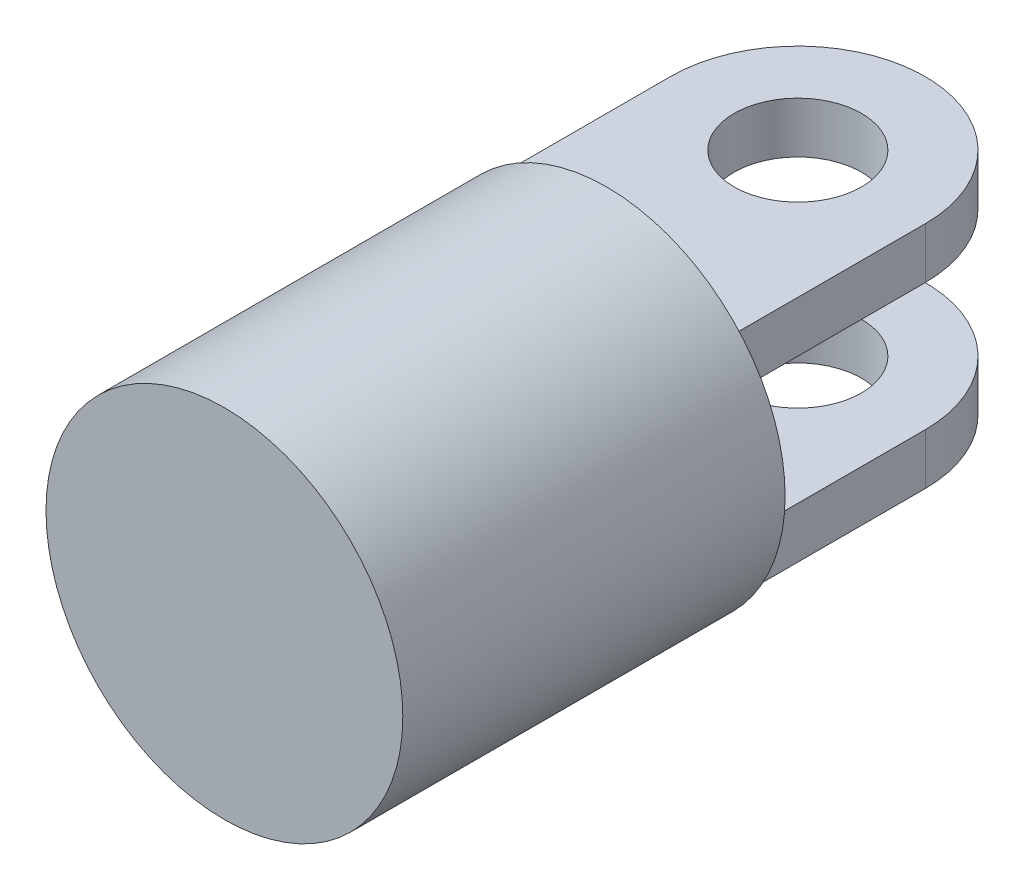
SolidWorks part; units mm, degrees
ref_plane "前视基准面" through (0, 0, 0) normal (0, 0, 1) x (1, 0, 0)
ref_plane "上视基准面" through (0, 0, 0) normal (0, 1, 0) x (1, 0, 0)
ref_plane "右视基准面" through (0, 0, 0) normal (1, 0, 0) x (0, 0, -1)
sketch "草图1" plane through (0, 0, 0) normal (0, 0, 1) x (1, 0, 0)
  circle A0 centre (0, 0) radius 14
  dimension "D1" = 28
extrude "凸台-拉伸1" add sketch "草图1" along normal blind 30
sketch "草图2" plane through (0, 0, 0) normal (0, 1, 0) x (1, 0, 0)
  line L0 (10, 15) -> (10, 0)
  line L1 (14, 0) -> (-14, 0) construction
  line L2 (-10, 15) -> (-10, 0)
  line L3 (-10, 0) -> (10, 0)
  arc A0 (10, 15) -> (-10, 15) centre (0, 15) ccw
  circle A1 centre (0, 15) radius 5
  dimension "D1" = 20
  dimension "D2" = 10
  dimension "D3" = 15
extrude "凸台-拉伸2" add sketch "草图2" along normal mid plane 18
extrude "切除-拉伸1" cut sketch "草图2<3>" against normal mid plane 10
sketch "草图2<3>" plane through (0, 0, 0) normal (0, 1, 0) x (1, 0, 0) same geometry as "草图2"
